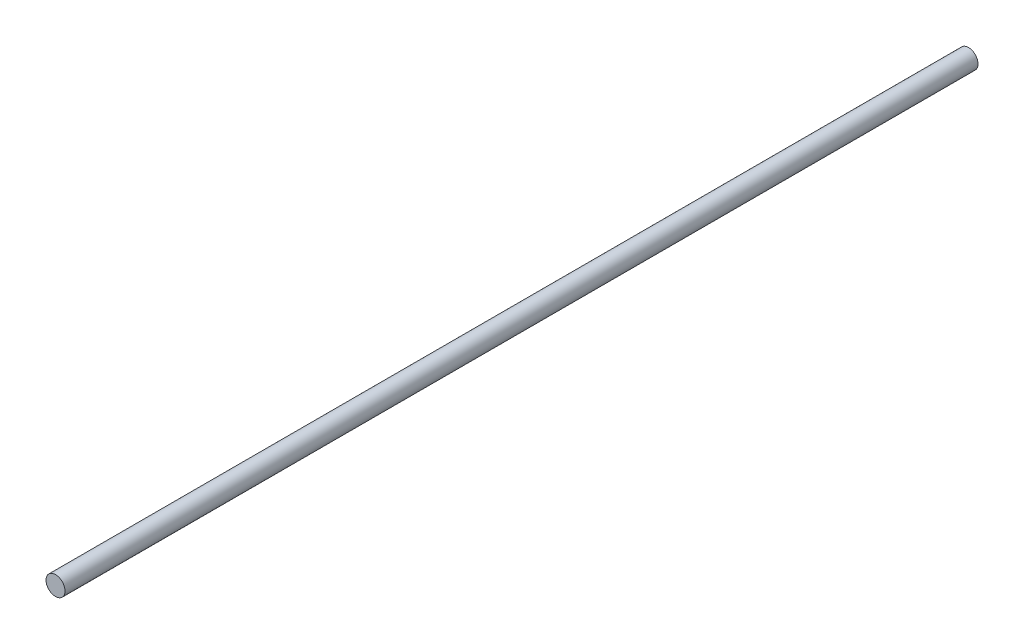
SolidWorks part; units mm, degrees
ref_plane "Front" through (0, 0, 0) normal (0, 0, 1) x (1, 0, 0)
ref_plane "Top" through (0, 0, 0) normal (0, 1, 0) x (1, 0, 0)
ref_plane "Right" through (0, 0, 0) normal (1, 0, 0) x (0, 0, -1)
sketch "Sketch1" plane through (0, 0, 0) normal (0, 0, 1) x (1, 0, 0)
  circle A0 centre (0, 0) radius 3.175
  dimension "D1" = 6.35
extrude "Extrude1" add sketch "Sketch1" along normal mid plane 304.8
chamfer "Chamfer1" [suppressed] distance 0.635 angle 45
equation "\"D1@Chamfer1\" = \"D1@Sketch1\" * .1"
